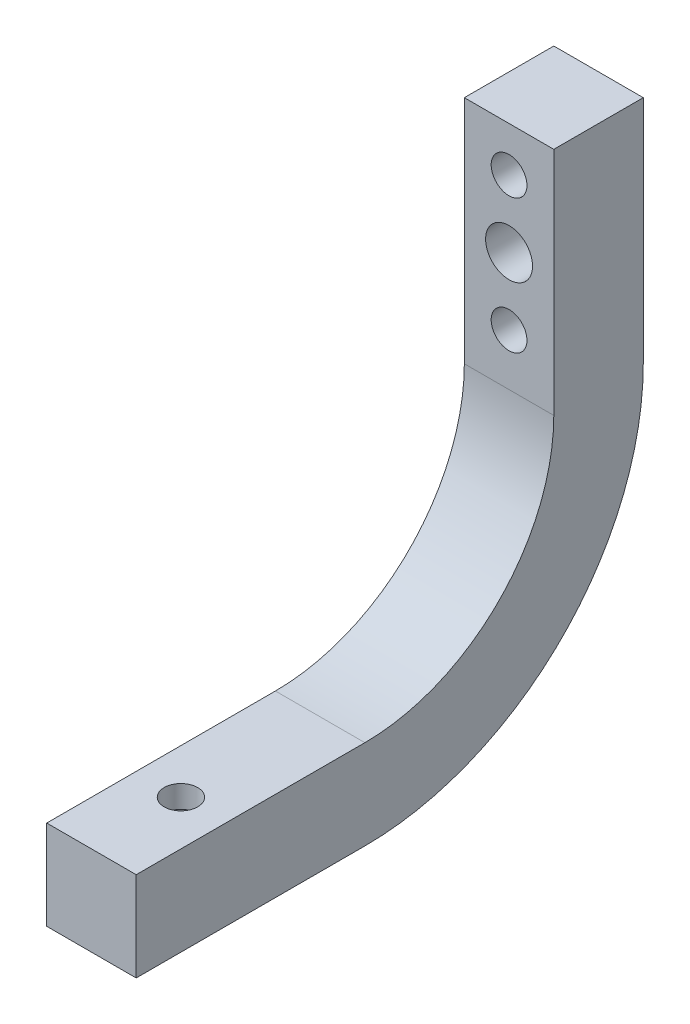
SolidWorks part; units mm, degrees
ref_plane "Front Plane" through (0, 0, 0) normal (0, 0, 1) x (1, 0, 0)
ref_plane "Top Plane" through (0, 0, 0) normal (0, 1, 0) x (1, 0, 0)
ref_plane "Right Plane" through (0, 0, 0) normal (1, 0, 0) x (0, 0, -1)
ref_axis "Z" through (0, 0, 47.607) along (0, 0, -1)
sketch "Sketch1" plane through (0, 0, 0) normal (1, 0, 0) x (0, 0, -1)
  line L0 (-8, 10) -> (0, 10)
  line L1 (0, 10) -> (0, -10.6067)
  line L2 (0, -18) -> (-17.5, -35.5) construction
  line L3 (-24.8933, -35.5) -> (-37.34, -35.5)
  line L4 (-37.34, -35.5) -> (-37.34, -27.5) construction
  line L5 (-37.34, -27.5) -> (-24.8933, -27.5)
  line L6 (-20.8137, -27.5) -> (-8, -14.6863) construction
  line L7 (-8, -10.6067) -> (-8, 10)
  line L8 (-14.4069, -21.0931) -> (-8.75, -26.75) construction
  line L9 (-24.8933, -27.5) -> (-20.8137, -27.5) construction
  line L10 (-37.34, -27.5) -> (-45.34, -27.5)
  line L11 (-37.34, -27.5) -> (-37.34, -35.5) construction
  line L12 (-37.34, -35.5) -> (-45.34, -35.5)
  line L13 (-45.34, -27.5) -> (-45.34, -35.5)
  line L14 (-8, -14.6863) -> (-8, -10.6067) construction
  line L15 (0, -10.6067) -> (0, -18) construction
  line L16 (-17.5, -35.5) -> (-24.8933, -35.5) construction
  arc A0 (-24.8933, -27.5) -> (-8, -10.6067) centre (-24.8933, -10.6067) ccw
  arc A1 (-24.8933, -35.5) -> (0, -10.6067) centre (-24.8933, -10.6067) ccw
  dimension "D2" = 37.34
  dimension "D3" = 35.5
  dimension "D4" = 10
  dimension "D5" = 135
  dimension "D6" = 17.5
  dimension "D7" = 8
  dimension "D8" = 12.4467
extrude "Boss-Extrude1" add sketch "Sketch1" along normal blind 4 and the other way blind 4
sketch "Sketch3" plane through (0, -27.5, 0) normal (0, 1, 0) x (1, 0, 0)
  line L0 (-55, 0) -> (55, 0) construction
  line L1 (0, -55) -> (0, 55) construction
  circle A0 centre (0, -37.34) radius 1.5
  dimension "D2" = 3
  dimension "D1" = 37.34
extrude "Cut-Extrude1" cut sketch "Sketch3" against normal through all
sketch "Sketch4" plane through (0, 0, 8) normal (0, 0, 1) x (1, 0, 0)
  line L0 (0, -6) -> (0, 6) construction
  circle A0 centre (0, 0) radius 2.1
  circle A1 centre (0, 6) radius 1.6
  circle A2 centre (0, -6) radius 1.6
  dimension "D1" = 4.2
  dimension "D3" = 3.2
  dimension "D2" = 12
extrude "Cut-Extrude2" cut sketch "Sketch4" against normal through all both and the other way through all
ref_axis "Axis1" through (0, -27.5, 37.34) along (0, 1, 0)
sketch "Sketch5" plane through (0, -35.5, 0) normal (0, -1, 0) x (1, 0, 0)
  circle A0 centre (0, 37.34) radius 2.275
  dimension "D1" = 4.55
extrude "Cut-Extrude3" cut sketch "Sketch5" against normal blind 6
sketch "Sketch6" plane through (0, -35.5, 0) normal (0, -1, 0) x (1, 0, 0)
  circle A0 centre (0, 37.34) radius 3.825
  dimension "D1" = 7.65
extrude "Cut-Extrude4" cut sketch "Sketch6" against normal blind 0.75
equation "\"rbracket-width\"=8"
equation "\"D1@Boss-Extrude1\"=\"rbracket-width\"/2"
equation "\"D2@Boss-Extrude1\"=\"rbracket-width\"/2"
equation "\"EyeCaptureRadius\"= ( \"EyeDiameter\" + \"EyeClearance\" ) / 2"
equation "\"rbracket_planetocenterline_dist\"= \"BasePlaneDistance\""
equation "\"D2@Sketch1\"=\"rbracket_planetocenterline_dist\""
equation "\"EyeDiameter\" = 35"
equation "\"BasePlaneDistance\" = \"EyeDiameter\"/2+19.84"
equation "\"EyeClearance\" = 2"
equation "\"D1@Sketch1\"=\"rbracket-width\""
equation "\"D3@Sketch1\"=(\"EyeDiameter\"+\"EyeClearance\"+\"EyeClearance\")/2 + \"L2Thickness\" + \"rbracket-width\""
equation "\"D4@Sketch1\"= 10"
equation "\"D6@Sketch1\"=\"EyeDiameter\"/2"
equation "\"D7@Sketch1\"=\"rbracket-width\""
equation "\"D1@Sketch3\"=\"BasePlaneDistance\""
equation "\"L2Thickness\" = 8"
equation "\"D8@Sketch1\"=\"rbracket_planetocenterline_dist\"/3"
equation "\"BearingFlangeOD\"= 7.5"
equation "\"BearingFlangeThickness\"= 0.75"
equation "\"BearingHousingID\"=4.5"
equation "\"BearingDepth\"= 6"
equation "\"D1@Sketch5\"=\"BearingHousingID\" + \"PrinterFilamentThickness\" * \"ApplyPrinterOffsets\" / 2"
equation "\"D1@Cut-Extrude3\"=\"BearingDepth\""
equation "\"D1@Sketch6\"=\"BearingFlangeOD\" + \"PrinterFilamentThickness\" * 1.5 * \"ApplyPrinterOffsets\""
equation "\"D1@Cut-Extrude4\"=\"BearingFlangeThickness\""
equation "\"PrinterFilamentThickness\"= 0.1"
equation "\"ApplyPrinterOffsets\"= 1"
